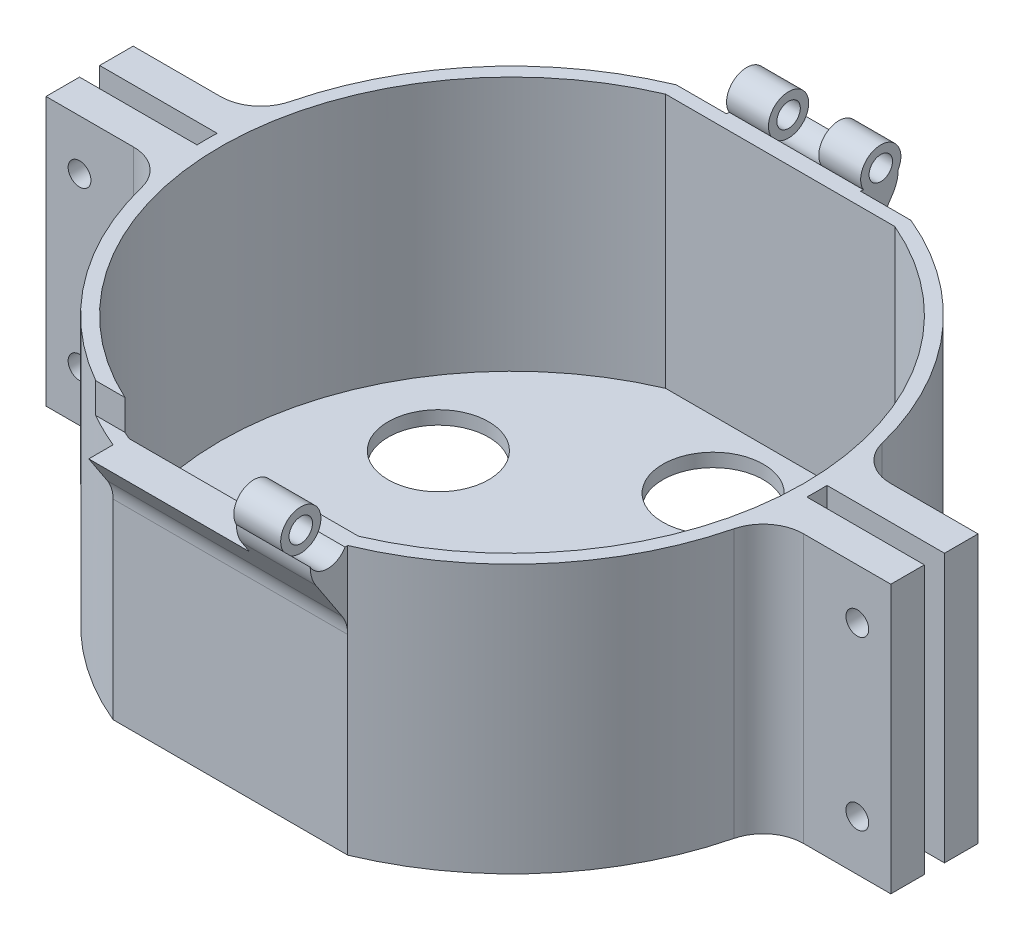
SolidWorks part; units mm, degrees
ref_plane "Front Plane" through (0, 0, 0) normal (0, 0, 1) x (1, 0, 0)
ref_plane "Top Plane" through (0, 0, 0) normal (0, 1, 0) x (1, 0, 0)
ref_plane "Right Plane" through (0, 0, 0) normal (1, 0, 0) x (0, 0, -1)
sketch "Sketch1" plane through (0, 0, 0) normal (0, 1, 0) x (1, 0, 0)
  line L0 (-17.5, 42) -> (17.5, 42)
  line L1 (-17.5, -42) -> (17.5, -42)
  line L2 (0, 0) -> (35.5206, 0) construction
  arc A0 (-17.5, 42) -> (-17.5, -42) centre (0, 0) ccw
  arc A1 (17.5, -42) -> (17.5, 42) centre (0, 0) ccw
  dimension "D1" = 91
  dimension "D2" = 42
  dimension "D3" = 42
extrude "Boss-Extrude1" add sketch "Sketch1" along normal blind 40
shell "Shell1" thickness 2 removed face at (0, 40, 0)
sketch "Sketch2" plane through (0, 2, 0) normal (0, 1, 0) x (1, 0, 0)
  circle A0 centre (0, 0) radius 3
  circle A1 centre (0, 30) radius 7.5
  circle A2 centre (25.9808, 15) radius 7.5
  circle A3 centre (25.9808, -15) radius 7.5
  circle A4 centre (0, -30) radius 7.5
  circle A5 centre (-25.9808, -15) radius 7.5
  circle A6 centre (-25.9808, 15) radius 7.5
  point P18 (0, 0)
  dimension "D1" = 6
  dimension "D2" = 15
  dimension "D3" = 30
  dimension "D4" = 6
extrude "Cut-Extrude1" cut sketch "Sketch2" against normal up to surface (2 mm away) up to face at (0, 0, 0)
sketch "Sketch3" plane through (0, 0, 0) normal (0, -1, 0) x (1, 0, 0)
  line L2 (0, 0) -> (-50.0606, 50.0606) construction
  line L3 (0, 0) -> (-30.2903, 0) construction
  line L4 (-35.8503, 28.0179) -> (-41.5072, 35.8503)
  line L5 (-41.5072, 35.8503) -> (-41.5072, 41.5072)
  line L6 (-41.5072, 41.5072) -> (-35.8503, 41.5072)
  line L7 (-35.8503, 41.5072) -> (-28.0179, 35.8503)
  arc A0 (-35.8503, 28.0179) -> (-28.0179, 35.8503) centre (0, 0) cw
  circle A1 centre (0, 0) radius 45.5 construction
  circle A2 centre (-35.8503, 35.8503) radius 3
  dimension "D2" = 6
  dimension "D1" = 45
  dimension "D3" = 50.7
  dimension "D4" = 8
extrude "Boss-Extrude2" [suppressed] add sketch "Sketch3" against normal blind 10
fillet "Fillet1" [suppressed] radius 5
pattern_circular "CirPattern1" [suppressed] count 4 over 360 of bodies 103
sketch "Sketch4" plane through (0, 0, 0) normal (1, 0, 0) x (0, 0, -1)
  line L0 (-42, 30) -> (-47.5981, 38.5)
  line L1 (-42, 40) -> (-42, 0) construction
  line L2 (-47.5981, 38.5) -> (-47.5981, 40)
  line L3 (-42.4019, 40) -> (-42, 40)
  line L4 (-42, 40) -> (-42, 30)
  line L5 (-42, 40) -> (-42, 44.2633) construction
  line L6 (-45, 38.5) -> (-46.9312, 38.5) construction
  arc A0 (-42.4019, 40) -> (-47.5981, 40) centre (-45, 41.5) ccw
  circle A1 centre (-45, 41.5) radius 1.75
  dimension "D1" = 6
  dimension "D2" = 3.5
  dimension "D3" = 10
  dimension "D4" = 5.5981
  dimension "D5" = 1.5
extrude "Boss-Extrude3" add sketch "Sketch4" along normal up to vertex (17.5 mm away) and the other way up to vertex (17.5 mm away) up to point (17.5, 40, 42) other way up to point (-17.5, 40, 42)
fillet "Fillet2" radius 5 2 edges at (0, 38.5, 47.5981) (0, 30, 42)
mirror "Mirror1" about plane through (0, 0, 0) normal (0, 0, 1) of "Boss-Extrude3"
fillet "Fillet3" radius 5 2 edges at (0, 38.5, -47.5981) (0, 30, -42)
sketch "Sketch5" plane through (17.5, 0, 0) normal (1, 0, 0) x (0, 0, -1)
  circle A1 centre (-45, 41.5) radius 3
extrude "Cut-Extrude2" cut sketch "Sketch5" against normal blind 4
sketch "Sketch6" plane through (0, 0, 0) normal (1, 0, 0) x (0, 0, -1)
  circle A1 centre (45, 41.5) radius 3
extrude "Cut-Extrude3" cut sketch "Sketch6" against normal blind 3.75 and the other way blind 3.75
sketch "Sketch7" plane through (-17.5, 0, 0) normal (-1, 0, 0) x (0, 0, 1)
  line L1 (-42, 28.5014) -> (-52, 28.5014)
  line L2 (-42, 28.5014) -> (-42, 48.5014)
  line L3 (-42, 48.5014) -> (-52, 48.5014)
  line L4 (-52, 28.5014) -> (-52, 48.5014)
  dimension "D1" = 10
  dimension "D2" = 20
extrude "Cut-Extrude4" cut sketch "Sketch7" against normal blind 7.5
sketch "Sketch8" plane through (-17.5, 0, 0) normal (-1, 0, 0) x (0, 0, 1)
  line L0 (45, 41.5) -> (51.7755, 41.5) construction
  line L5 (39.5, 35.5) -> (50.5, 35.5)
  line L6 (39.5, 35.5) -> (39.5, 47.5)
  line L7 (39.5, 47.5) -> (50.5, 47.5)
  line L8 (50.5, 35.5) -> (50.5, 47.5)
  line L9 (45, 41.5) -> (45, 46.629) construction
  point P5 (45, 35.5)
  point P9 (50.5, 41.5)
  dimension "D1" = 11
  dimension "D2" = 12
sketch "Sketch9" plane through (17.5, 0, 0) normal (1, 0, 0) x (0, 0, -1)
  line L0 (42, 28.5014) -> (42, 0) construction
  line L1 (42, 25.5014) -> (52, 25.5014)
  line L2 (42, 25.5014) -> (42, 50.5014)
  line L3 (42, 50.5014) -> (52, 50.5014)
  line L4 (52, 25.5014) -> (52, 50.5014)
  dimension "D1" = 10
  dimension "D2" = 25
  dimension "D3" = 3
extrude "Cut-Extrude6" cut sketch "Sketch9" against normal blind 7.5
extrude "Cut-Extrude7" cut sketch "Sketch8" against normal blind 24 and the other way up to surface other way up to face at (-28.7, 21.7003, 8.4)
fillet "Fillet4" [suppressed] radius 5
sketch "Sketch10" plane through (0, 0, 0) normal (0, -1, 0) x (1, 0, 0)
  line L0 (0, 0) -> (78.512, 0) construction
  line L1 (45.4753, 1.5) -> (63, 1.5)
  line L2 (63, 1.5) -> (63, 6.5)
  line L3 (63, 6.5) -> (49.96, 6.5)
  line L4 (0, 0) -> (0, 52.8713) construction
  arc A0 (17.5, -42) -> (17.5, 42) centre (0, 0) ccw construction
  arc A1 (49.96, 6.5) -> (44.1394, 11.0437) centre (49.96, 12.5) cw
  arc A2 (45.4753, 1.5) -> (44.1394, 11.0437) centre (0, 0) ccw
  dimension "D4" = 6
  dimension "D1" = 3
  dimension "D2" = 5
  dimension "D3" = 126
extrude "Boss-Extrude4" add sketch "Sketch10" against normal up to surface (40 mm away) up to face at (2.2771, 40, -5.075)
hole_wizard "M3 Clearance Hole1" positions "Sketch11" profile "Sketch12" hole size "M3" standard "ANSI Metric" end condition through all
sketch "Sketch11" plane through (0, 0, 6.5) normal (0, 0, 1) x (1, 0, 0)
  line L0 (63, 20) -> (80.4921, 20) construction
  line L1 (63, 40) -> (63, 0) construction
  point P9 (58, 32.5)
  point P11 (58, 7.5)
  point P19 (0, 0)
  point P20 (0, 0)
  point P21 (53.0275, 8.2489)
  point P22 (80.4921, 20)
  dimension "D1" = 25
  dimension "D2" = 5
sketch "Sketch12" plane through (58, 7.5, 6.5) normal (1, 0, 0) x (0, -1, 0)
  line L0 (0, 0) -> (0, 54.5)
  line L1 (0, 54.5) -> (1.7, 54.5)
  line L2 (1.7, 54.5) -> (1.7, 0)
  line L5 (1.7, 0) -> (0, 0)
  line L11 (0, -6.35) -> (0, 107.95) construction
  dimension "Thru Hole Dia." = 3.4
  dimension "Thru Hole Depth" = 54.5
mirror "Mirror2" about plane through (0, 0, 0) normal (1, 0, 0) of "M3 Clearance Hole1", "Boss-Extrude4" second plane through (0, 0, 0) second plane normal (0, 0, 1)
